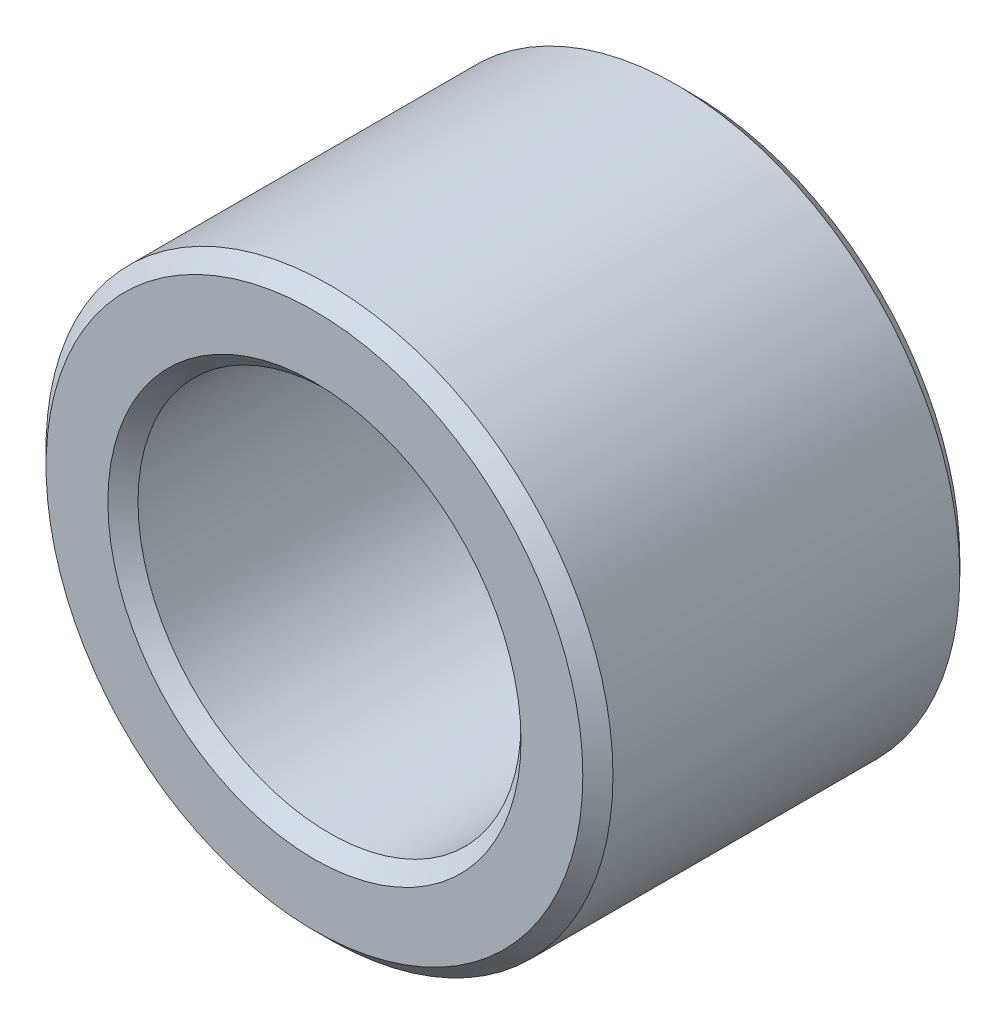
SolidWorks part; units mm, degrees
ref_plane "Front Plane" through (0, 0, 0) normal (0, 0, 1) x (1, 0, 0)
ref_plane "Top Plane" through (0, 0, 0) normal (0, 1, 0) x (1, 0, 0)
ref_plane "Right Plane" through (0, 0, 0) normal (1, 0, 0) x (0, 0, -1)
sketch "Sketch1" plane through (0, 0, 0) normal (0, 0, 1) x (1, 0, 0)
  circle A0 centre (0, 0) radius 4.7752
  circle A1 centre (0, 0) radius 3.2258
  dimension "D1" = 9.5504
  dimension "ID" = 6.4516
extrude "Extrude1" add sketch "Sketch1" along normal mid plane 6.35
sketch "Sketch2" plane through (0, 0, 0) normal (1, 0, 0) x (0, 0, -1)
  line L0 (-3.175, -3.2258) -> (3.175, -3.2258) construction
  line L3 (3.175, 3.2258) -> (-3.175, 3.2258) construction
  line L5 (-3.175, -3.2258) -> (3.175, -3.2258)
  line L6 (3.175, 3.2258) -> (-3.175, 3.2258)
sketch "Sketch4" plane through (0, 0, 3.175) normal (0, 0, 1) x (1, 0, 0)
  line L0 (0, 0) -> (-2.281, 2.281)
  line L1 (0, -6.985) -> (0, 6.985) construction
  circle A0 centre (0, 0) radius 3.2258 construction
  dimension "D1" = 45
chamfer "Chamfer1" distance 0.254 angle 45 4 edges at (3.2258, 0, -3.175) (4.7752, 0, -3.175) (3.2258, 0, 3.175) (4.7752, 0, 3.175)
